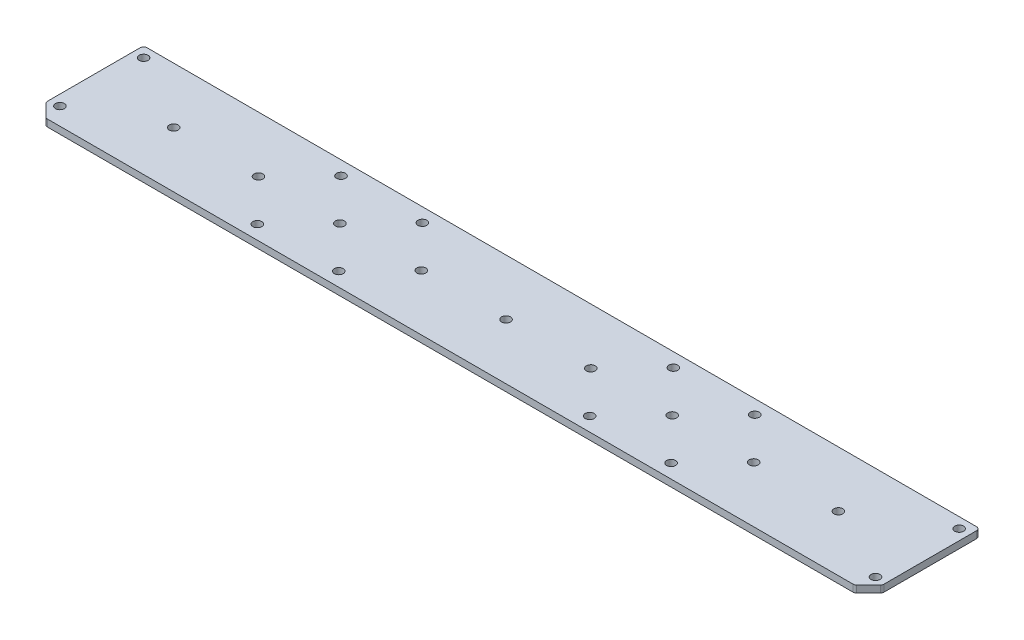
SolidWorks part; units mm, degrees
ref_plane "Front Plane" through (0, 0, 0) normal (0, 0, 1) x (1, 0, 0)
ref_plane "Top Plane" through (0, 0, 0) normal (0, 1, 0) x (1, 0, 0)
ref_plane "Right Plane" through (0, 0, 0) normal (1, 0, 0) x (0, 0, -1)
sketch "Sketch2" plane through (0, 0, 0) normal (0, 1, 0) x (1, 0, 0)
  line L0 (0, 7.0076) -> (0, 50.8)
  line L1 (0, 50.8) -> (381, 50.8)
  line L2 (381, 50.8) -> (381, 7.0076)
  line L3 (373.9924, 0) -> (7.0076, 0)
  line L4 (5.885, 0.465) -> (0.465, 5.885) construction
  line L5 (5.885, 0.465) -> (0.465, 5.885)
  line L6 (375.115, 0.465) -> (380.535, 5.885) construction
  line L7 (375.115, 0.465) -> (380.535, 5.885)
  line L8 (361.7156, 50.8) -> (379.4125, 50.8) construction
  arc A0 (5.885, 0.465) -> (7.0076, 0) centre (7.0076, 1.5875) ccw construction
  arc A1 (0, 7.0076) -> (0.465, 5.885) centre (1.5875, 7.0076) ccw construction
  arc A2 (5.885, 0.465) -> (7.0076, 0) centre (7.0076, 1.5875) ccw
  arc A3 (0, 7.0076) -> (0.465, 5.885) centre (1.5875, 7.0076) ccw
  arc A4 (373.9924, 0) -> (375.115, 0.465) centre (373.9924, 1.5875) ccw construction
  arc A6 (373.9924, 0) -> (375.115, 0.465) centre (373.9924, 1.5875) ccw
  arc A8 (380.535, 5.885) -> (381, 7.0076) centre (379.4125, 7.0076) ccw construction
  arc A9 (380.535, 5.885) -> (381, 7.0076) centre (379.4125, 7.0076) ccw
extrude "Boss-Extrude1" add sketch "Sketch2" along normal blind 3.175
sketch "Sketch3" plane through (0, 0, 0) normal (0, 1, 0) x (1, 0, 0)
  circle A25 centre (4.7625, 7.9375) radius 2.032 construction
  circle A31 centre (4.7625, 46.0375) radius 2.032 construction
  circle A63 centre (376.2375, 7.9375) radius 2.032 construction
  circle A64 centre (376.2375, 46.0375) radius 2.032 construction
  circle A67 centre (4.7625, 7.9375) radius 2.032
  circle A68 centre (4.7625, 46.0375) radius 2.032
  circle A72 centre (376.2375, 7.9375) radius 2.032
  circle A73 centre (376.2375, 46.0375) radius 2.032
  circle A123 centre (341.884, 25.4) radius 2.032 construction
  circle A124 centre (247.65, 44.45) radius 2.032 construction
  circle A125 centre (284.734, 44.45) radius 2.032 construction
  circle A128 centre (247.65, 6.35) radius 2.032 construction
  circle A129 centre (284.734, 6.35) radius 2.032 construction
  circle A132 centre (190.5, 25.4) radius 2.032 construction
  circle A134 centre (170.434, 6.35) radius 2.032 construction
  circle A135 centre (133.35, 44.45) radius 2.032 construction
  circle A136 centre (96.266, 44.45) radius 2.032 construction
  circle A137 centre (96.266, 6.35) radius 2.032 construction
  circle A140 centre (77.724, 25.4) radius 2.032 construction
  circle A141 centre (39.116, 25.4) radius 2.032 construction
  circle A142 centre (341.884, 25.4) radius 2.032
  circle A143 centre (247.65, 44.45) radius 2.032
  circle A144 centre (284.734, 44.45) radius 2.032
  circle A147 centre (247.65, 6.35) radius 2.032
  circle A148 centre (284.734, 6.35) radius 2.032
  circle A151 centre (190.5, 25.4) radius 2.032
  circle A154 centre (133.35, 44.45) radius 2.032
  circle A155 centre (96.266, 44.45) radius 2.032
  circle A156 centre (96.266, 6.35) radius 2.032
  circle A159 centre (77.724, 25.4) radius 2.032
  circle A160 centre (39.116, 25.4) radius 2.032
  circle A161 centre (151.892, 25.4) radius 2.032
  circle A162 centre (229.108, 25.4) radius 2.032
  circle A163 centre (266.192, 25.4) radius 2.032
  circle A164 centre (303.276, 25.4) radius 2.032
  circle A165 centre (151.892, 25.4) radius 2.3813 construction
  circle A166 centre (229.108, 25.4) radius 2.3813 construction
  circle A167 centre (266.192, 25.4) radius 2.3813 construction
  circle A168 centre (303.276, 25.4) radius 2.3813 construction
  circle A169 centre (133.35, 6.35) radius 2.032
  circle A170 centre (114.808, 25.4) radius 2.032 construction
  circle A171 centre (114.808, 25.4) radius 2.032
  point P83 (0, 0)
  point P94 (0, 0)
extrude "Cut-Extrude1" cut sketch "Sketch3" along normal through all
fillet "Fillet1" radius 1.5875 2 edges at (0, 1.5875, -50.8) (381, 1.5875, -50.8)
